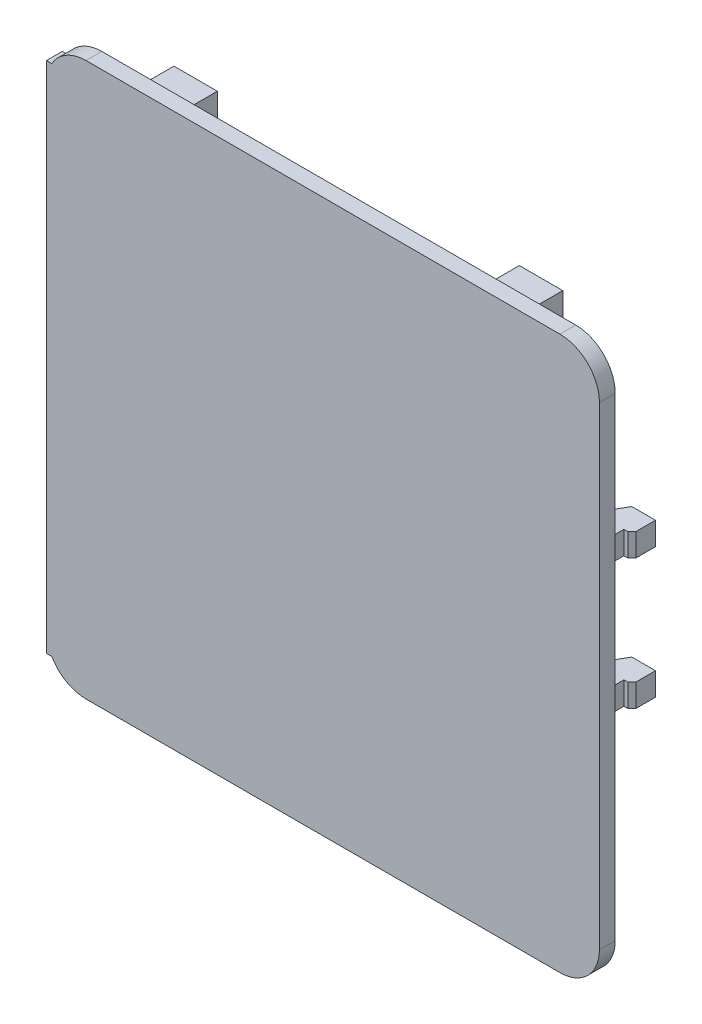
SolidWorks part; units mm, degrees
ref_plane "前视基准面" through (0, 0, 0) normal (0, 0, 1) x (1, 0, 0)
ref_plane "上视基准面" through (0, 0, 0) normal (0, 1, 0) x (1, 0, 0)
ref_plane "右视基准面" through (0, 0, 0) normal (1, 0, 0) x (0, 0, -1)
other "Configuration Table"
sketch "草图1" plane through (0, 0, 0) normal (0, 0, 1) x (1, 0, 0)
  line L0 (-30, -35) -> (30, -35) construction
  line L1 (35, -30) -> (35, 30) construction
  line L2 (30, 35) -> (-30, 35) construction
  line L3 (-30, -35) -> (30, -35)
  line L4 (35, -30) -> (35, 30)
  line L5 (30, 35) -> (-30, 35)
  line L9 (-35.8467, -30) -> (-34.8301, -30) construction
  line L10 (-35, -30) -> (-35, 30)
  line L11 (-35, -30) -> (-35, -32.5)
  line L12 (-34.3301, -32.5) -> (-35.8467, -32.5) construction
  line L13 (-35, -32.5) -> (-34.3301, -32.5)
  line L14 (-35, 30) -> (-35, 32.5)
  line L15 (-34.3301, 32.5) -> (-35.8467, 32.5) construction
  line L16 (-35, 32.5) -> (-34.3301, 32.5)
  arc A0 (30, -35) -> (35, -30) centre (30, -30) ccw construction
  arc A1 (35, 30) -> (30, 35) centre (30, 30) ccw construction
  arc A2 (30, -35) -> (35, -30) centre (30, -30) ccw
  arc A3 (35, 30) -> (30, 35) centre (30, 30) ccw
  arc A4 (-30, 35) -> (-34.3301, 32.5) centre (-30, 30) ccw
  arc A5 (-34.3301, -32.5) -> (-30, -35) centre (-30, -30) ccw
  arc A6 (-34.3301, -32.5) -> (-30, -35) centre (-30, -30) ccw construction
extrude "凸台-拉伸1" add sketch "草图1" along normal blind 2
sketch "草图2" plane through (0, 0, 0) normal (0, 0, -1) x (-1, 0, 0)
  line L0 (25.8672, -32.95) -> (25.8672, -29.95)
  line L1 (20.3672, -29.95) -> (20.3672, -32.95)
  line L2 (20.3672, -32.95) -> (25.8672, -32.95)
  line L3 (30, -35) -> (-30, -35) construction
  line L4 (20.3672, 32.95) -> (20.3672, 29.95)
  line L5 (25.8672, 29.95) -> (25.8672, 32.95)
  line L6 (25.8672, 32.95) -> (20.3672, 32.95)
  line L7 (-30, 35) -> (30, 35) construction
  line L8 (-23.357, -29.95) -> (-23.357, -32.95)
  line L9 (-23.357, -32.95) -> (-17.857, -32.95)
  line L10 (-17.857, -32.95) -> (-17.857, -29.95)
  line L11 (-23.357, 32.95) -> (-17.857, 32.95)
  line L12 (-17.857, 32.95) -> (-17.857, 29.95)
  line L13 (-23.357, 29.95) -> (-23.357, 32.95)
  arc A0 (25.8672, -29.95) -> (20.3672, -29.95) centre (23.1172, -29.95) ccw
  arc A1 (20.3672, 29.95) -> (25.8672, 29.95) centre (23.1172, 29.95) ccw
  arc A2 (-17.857, -29.95) -> (-23.357, -29.95) centre (-20.607, -29.95) ccw
  arc A3 (-17.857, 29.95) -> (-23.357, 29.95) centre (-20.607, 29.95) cw
  dimension "D1" = 2.05
  dimension "D2" = 3
  dimension "D3" = 5.5
  dimension "D4" = 2.05
  dimension "D5" = 5.5
  dimension "D6" = 3
  dimension "D7" = 2.05
  dimension "D8" = 5.5
  dimension "D9" = 3
  dimension "D10" = 5.5
  dimension "D11" = 2.05
  dimension "D12" = 3
extrude "凸台-拉伸2" add sketch "草图2" along normal blind 5
sketch "草图3" plane through (0, 0, 0) normal (0, 0, -1) x (-1, 0, 0)
  line L0 (30, -35) -> (-30, -35) construction
  line L1 (32.9, -29.95) -> (30.9, -29.95)
  line L2 (32.9, -29.95) -> (32.9, -28.05)
  line L3 (32.9, -28.05) -> (30.9, -28.05)
  line L4 (30.9, -29.95) -> (30.9, -28.05)
  line L5 (35, 32.5) -> (35, -32.5) construction
  line L6 (-30, 35) -> (30, 35) construction
  line L7 (32.9, 22.95) -> (30.9, 22.95)
  line L8 (32.9, 22.95) -> (32.9, 20.05)
  line L9 (32.9, 20.05) -> (30.9, 20.05)
  line L10 (30.9, 22.95) -> (30.9, 20.05)
  line L11 (-35, -30) -> (-35, 30) construction
  line L12 (-32.9, -4.05) -> (-30.9, -4.05)
  line L13 (-32.9, -4.05) -> (-32.9, -6.95)
  line L14 (-32.9, -6.95) -> (-30.9, -6.95)
  line L15 (-30.9, -4.05) -> (-30.9, -6.95)
  line L17 (-32.9, 12.45) -> (-30.9, 12.45)
  line L18 (-32.9, 12.45) -> (-32.9, 9.55)
  line L19 (-32.9, 9.55) -> (-30.9, 9.55)
  line L20 (-30.9, 12.45) -> (-30.9, 9.55)
  dimension "D1" = 2
  dimension "D2" = 1.9
  dimension "D3" = 5.05
  dimension "D4" = 2.1
  dimension "D5" = 2
  dimension "D6" = 2.9
  dimension "D7" = 12.05
  dimension "D8" = 2.1
  dimension "D9" = 2
  dimension "D10" = 2.9
  dimension "D11" = 28.05
  dimension "D12" = 2.1
  dimension "D13" = 2
  dimension "D14" = 2.9
  dimension "D15" = 2.1
  dimension "D16" = 22.55
extrude "凸台-拉伸3" add sketch "草图3" along normal blind 3.2
sketch "草图4" plane through (0, 0, -3.2) normal (0, 0, -1) x (-1, 0, 0)
  line L0 (32.9, -28.05) -> (30.9, -28.05) construction
  line L1 (30.9, -29.95) -> (34.05, -29.95)
  line L2 (30.9, -29.95) -> (30.9, -28.05)
  line L3 (30.9, -28.05) -> (34.05, -28.05)
  line L4 (34.05, -29.95) -> (34.05, -28.05)
  line L5 (30.9, 20.05) -> (34.05, 20.05)
  line L6 (30.9, 20.05) -> (30.9, 22.95)
  line L7 (30.9, 22.95) -> (34.05, 22.95)
  line L8 (34.05, 20.05) -> (34.05, 22.95)
  line L9 (32.9, 22.95) -> (30.9, 22.95) construction
  line L10 (-32.9, -6.95) -> (-30.9, -6.95) construction
  line L11 (-30.9, -4.05) -> (-33.9, -4.05)
  line L12 (-30.9, -4.05) -> (-30.9, -6.95)
  line L13 (-30.9, -6.95) -> (-33.9, -6.95)
  line L14 (-33.9, -4.05) -> (-33.9, -6.95)
  line L15 (-32.9, 9.55) -> (-30.9, 9.55) construction
  line L16 (-30.9, 12.45) -> (-33.9, 12.45)
  line L17 (-30.9, 12.45) -> (-30.9, 9.55)
  line L18 (-30.9, 9.55) -> (-33.9, 9.55)
  line L19 (-33.9, 12.45) -> (-33.9, 9.55)
  dimension "D1" = 3.15
  dimension "D2" = 3.15
  dimension "D3" = 3
  dimension "D4" = 3
extrude "凸台-拉伸4" add sketch "草图4" along normal blind 3
sketch "草图6" plane through (0, 0, -6.2) normal (0, 0, -1) x (-1, 0, 0)
  line L1 (30.9, 22.95) -> (34.05, 22.95)
  line L2 (30.9, 22.95) -> (30.9, 20.05)
  line L3 (30.9, 20.05) -> (34.05, 20.05)
  line L4 (34.05, 22.95) -> (34.05, 20.05)
  line L5 (30.9, -28.05) -> (34.05, -28.05)
  line L6 (30.9, -28.05) -> (30.9, -29.95)
  line L7 (30.9, -29.95) -> (34.05, -29.95)
  line L8 (34.05, -28.05) -> (34.05, -29.95)
extrude "凸台-拉伸5" add sketch "草图6" along normal blind 0.7
sketch "草图7" plane through (0, -29.95, 0) normal (0, -1, 0) x (1, 0, 0)
  line L0 (-30.9, -6.9) -> (-26.9163, 0)
  line L1 (-30, 0) -> (30, 0) construction
  line L2 (-26.9163, 0) -> (-30.9, 0)
  line L3 (-30.9, 0) -> (-30.9, -6.9)
  dimension "D1" = 60
extrude "凸台-拉伸6" add sketch "草图7" against normal up to surface (1.9 mm away) up to face at (-32.6167, -28.05, -3.3667)
sketch "草图8" plane through (0, 22.95, 0) normal (0, 1, 0) x (1, 0, 0)
  line L0 (-30.9, 6.9) -> (-26.9163, 0)
  line L1 (-26.9163, 0) -> (-30.9, 0)
  line L2 (-30.9, 0) -> (-30.9, 6.9)
extrude "凸台-拉伸7" add sketch "草图8" against normal up to surface (2.9 mm away) up to face at (-32.6167, 20.05, -3.3667)
sketch "草图9" plane through (0, 12.45, 0) normal (0, 1, 0) x (1, 0, 0)
  line L0 (30.9, 6.2) -> (27.3204, 0)
  line L1 (30, 0) -> (-30, 0) construction
  line L2 (27.3204, 0) -> (30.9, 0)
  line L3 (30.9, 0) -> (30.9, 6.2)
  dimension "D1" = 60
extrude "凸台-拉伸8" add sketch "草图9" against normal up to surface (2.9 mm away) up to face at (32.5667, 9.55, -3.1333)
sketch "草图10" plane through (0, -6.95, 0) normal (0, -1, 0) x (1, 0, 0)
  line L0 (30.9, -6.2) -> (27.3204, 0)
  line L1 (27.3204, 0) -> (30.9, 0)
  line L2 (30.9, 0) -> (30.9, -6.2)
extrude "凸台-拉伸9" add sketch "草图10" against normal up to surface (2.9 mm away) up to face at (32.5667, -4.05, -3.1333)
fillet "圆角1" radius 2 8 edges at (-29.9081, 20.05, 0) (-29.9081, 22.95, 0) (30.1102, 12.45, 0) (30.1102, -4.05, 0) (30.1102, -6.95, 0) (30.1102, 9.55, 0) (-29.9081, -29.95, 0) (-29.9081, -28.05, 0)
sketch "草图11" plane through (0, 12.45, 0) normal (0, 1, 0) x (1, 0, 0)
  line L0 (33.4, 3.2) -> (33.9, 3.7)
  line L1 (32.9, 3.2) -> (33.9, 3.2) construction
  line L2 (33.9, 6.2) -> (33.9, 3.2) construction
  line L3 (33.9, 3.7) -> (33.9, 3.2)
  line L4 (33.9, 3.2) -> (33.4, 3.2)
extrude "切除-拉伸1" cut sketch "草图11" against normal up to surface (19.4 mm away) up to face at (32.1625, -6.95, -3.8)
